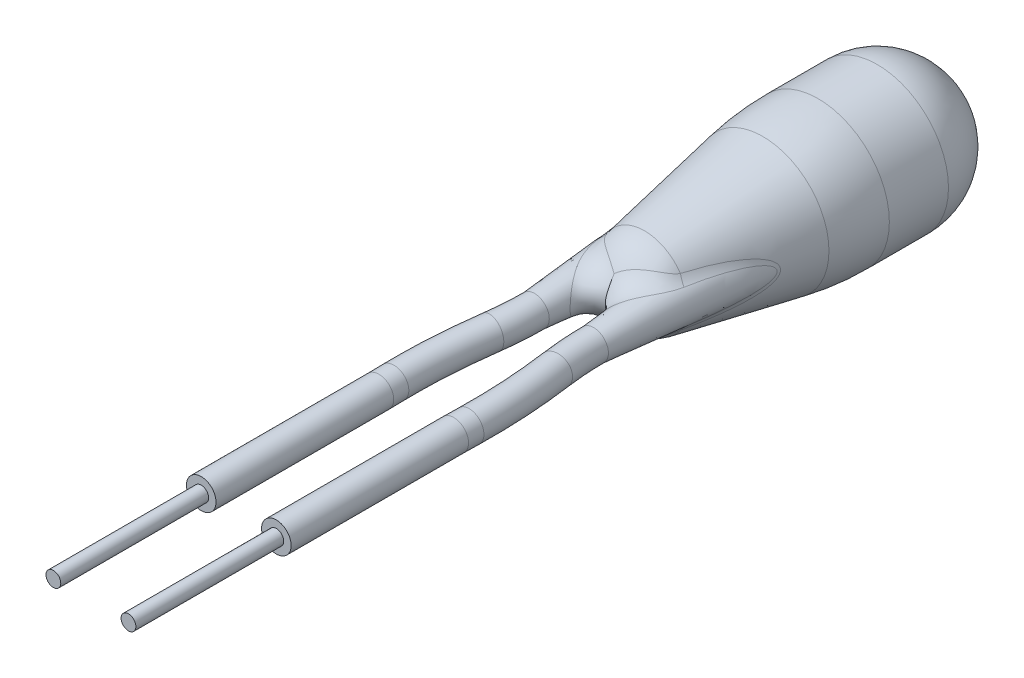
SolidWorks part; units mm, degrees
ref_plane "Спереди" through (0, 0, 0) normal (0, 0, 1) x (1, 0, 0)
ref_plane "Сверху" through (0, 0, 0) normal (0, 1, 0) x (1, 0, 0)
ref_plane "Справа" through (0, 0, 0) normal (1, 0, 0) x (0, 0, -1)
sketch "Эскиз1" plane through (0, 0, 0) normal (0, 1, 0) x (1, 0, 0)
  line L1 (1.205, 5.295) -> (1.205, 4.295)
  line L3 (0.7368, 1.36) -> (1.1171, 3.3617)
  line L4 (0, 0) -> (0, 6.5) construction
  line L5 (0, 6.5) -> (0, 0.75)
  arc A0 (0, 6.5) -> (1.205, 5.295) centre (0, 5.295) cw
  arc A3 (0, 0.75) -> (0.7368, 1.36) centre (0, 1.5) ccw
  arc A5 (1.1171, 3.3617) -> (1.205, 4.295) centre (-3.795, 4.295) ccw
  dimension "D1" = 6.5
  dimension "D3" = 1
  dimension "D4" = 0.75
  dimension "D6" = 5
  dimension "D2" = 1.205
  dimension "D5" = 1.5
revolve "Body" add sketch "Эскиз1" angle 360 about L4
sketch "Эскиз2" plane through (0, 0, 0) normal (0, 0, 1) x (1, 0, 0)
  line L0 (-0.5, 0) -> (0.5, 0) construction
  circle A0 centre (-0.5, 0) radius 0.25
  circle A1 centre (0.5, 0) radius 0.25
  point P4 (0, 0)
  dimension "D1" = 0.5
  dimension "D2" = 1
extrude "Wire entry" add sketch "Эскиз2" against normal blind 5 draft 5 draft outward yes
fillet "Скругление1" radius 0.5 4 edges at (0.9805, -0.0289, -2.6451) (-0.1831, -0.021, -0.773) (0.1831, 0.021, -0.773) (-0.9805, 0.0289, -2.6451)
sketch "Эскиз3" plane through (0, 0, 0) normal (0, 1, 0) x (1, 0, 0)
  line L0 (-0.5, 0) -> (0.5, 0) construction
  line L1 (-0.5, 0) -> (-0.5, 5.295)
  line L2 (-0.635, -2.5) -> (0.635, -2.5) construction
  line L3 (-0.635, -2.5) -> (-0.635, -5.5)
  line L4 (0.635, -2.5) -> (0.635, -5.5)
  line L5 (0.5, 0) -> (0.5, 5.295)
  line L6 (-0.6398, -2.24) -> (-0.635, -2.5)
  line L7 (0.635, -2.5) -> (0.6398, -2.24)
  arc A0 (-0.5472, -0.6852) -> (-0.5, 0) centre (-5.5, 0) ccw
  arc A1 (0.5, 0) -> (0.5472, -0.6852) centre (5.5, 0) ccw
  arc A2 (-0.5, 5.295) -> (0.5, 5.295) centre (0, 5.295) cw
  arc A3 (1.205, 5.295) -> (-1.205, 5.295) centre (0, 5.295) ccw construction
  arc A4 (-0.5472, -0.6852) -> (-0.6398, -2.24) centre (9.3585, -2.0555) ccw
  arc A5 (0.5472, -0.6852) -> (0.6398, -2.24) centre (-9.3585, -2.0555) cw
  point P6 (0, 0)
  point P11 (0, -2.5)
  point P14 (-0.6581, -1.2475)
  point P17 (0, 0)
  point P24 (0.6581, -1.2475)
  dimension "D1" = 1
  dimension "D2" = 5
  dimension "D6" = 10
  dimension "D7" = 10
  dimension "D3" = 1.27
  dimension "D4" = 2.5
  dimension "D5" = 3
sweep "Wire conductor" add path "Эскиз3" circular profile diameter 0.25 parameters "D3"=0.25
sweep "Wire isolation" add path "Эскиз3<4>" circular profile diameter 0.5 parameters "D3"=0.5
sketch "Эскиз3<4>" plane through (0, 0, 0) normal (0, 1, 0) x (1, 0, 0) same geometry as "Эскиз3"
sketch "Эскиз37" plane through (0, 0, 5.5) normal (0, 0, 1) x (1, 0, 0)
  line L0 (-0.635, 0) -> (0.635, 0) construction
  line L1 (-0.5472, 0) -> (-0.6415, 0) construction
  circle A0 centre (-0.635, 0) radius 0.125
  circle A1 centre (0.635, 0) radius 0.125
  point P9 (-0.5357, 0)
  point P10 (-0.635, 0)
  point P12 (-0.6415, 0)
  dimension "D1" = 0.25
extrude "Бобышка-Вытянуть1" add sketch "Эскиз37" along normal blind 2.5
